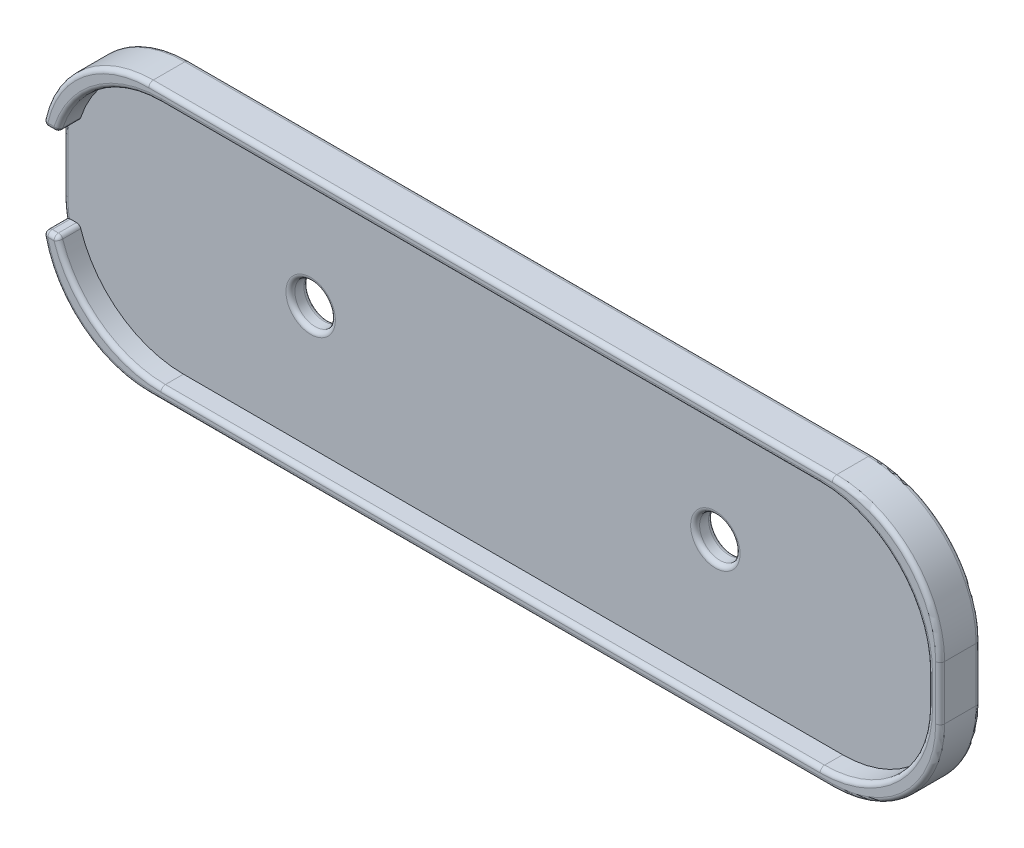
SolidWorks part; units mm, degrees
ref_plane "Front Plane" through (0, 0, 0) normal (0, 0, 1) x (1, 0, 0)
ref_plane "Top Plane" through (0, 0, 0) normal (0, 1, 0) x (1, 0, 0)
ref_plane "Right Plane" through (0, 0, 0) normal (1, 0, 0) x (0, 0, -1)
sketch "Sketch1" plane through (0, 0, 0) normal (0, 0, 1) x (1, 0, 0)
  line L1 (-50, 15) -> (50, 15)
  line L2 (-50, 15) -> (-50, -15)
  line L3 (-50, -15) -> (50, -15)
  line L4 (50, 15) -> (50, -15)
  line L5 (-50, 15) -> (50, -15) construction
  line L6 (-50, -15) -> (50, 15) construction
  point P0 (0, 0)
  dimension "D1" = 30
  dimension "D2" = 100
extrude "Boss-Extrude1" add sketch "Sketch1" along normal blind 2
sketch "Sketch2" plane through (0, 0, 2) normal (0, 0, 1) x (1, 0, 0)
  line L1 (-50, 15) -> (50, 15)
  line L2 (-50, 15) -> (-50, -15)
  line L3 (-50, -15) -> (50, -15)
  line L4 (50, 15) -> (50, -15)
  line L5 (48.65, 13.65) -> (-48.65, 13.65)
  line L6 (48.65, 13.65) -> (48.65, -13.65)
  line L7 (48.65, -13.65) -> (-48.65, -13.65)
  line L8 (-48.65, 13.65) -> (-48.65, -13.65)
  line L9 (48.65, 13.65) -> (-48.65, -13.65) construction
  line L10 (48.65, -13.65) -> (-48.65, 13.65) construction
  point P6 (0, 0)
  dimension "D1" = 1.35
  dimension "D2" = 1.35
extrude "Boss-Extrude2" add sketch "Sketch2" along normal blind 2.5
fillet "Fillet1" radius 12 8 edges at (-50, 15, 2.25) (50, 15, 2.25) (50, -15, 2.25) (-50, -15, 2.25) (48.65, -13.65, 3.25) (-48.65, -13.65, 3.25) (48.65, 13.65, 3.25) (-48.65, 13.65, 3.25)
sketch "Sketch3" plane through (0, 0, 2) normal (0, 0, 1) x (1, 0, 0)
  line L0 (-50, 3) -> (-50, -3) construction
  line L1 (-45, 5) -> (-55, 5)
  line L2 (-45, 5) -> (-45, -5)
  line L3 (-45, -5) -> (-55, -5)
  line L4 (-55, 5) -> (-55, -5)
  line L5 (-45, 5) -> (-55, -5) construction
  line L6 (-45, -5) -> (-55, 5) construction
  point P0 (-50, 0)
  dimension "D1" = 10
  dimension "D2" = 10
extrude "Cut-Extrude1" cut sketch "Sketch3" along normal through all
fillet "Fillet2" radius 0.5 31 edges at (0, -15, 0) (46.4853, -11.4853, 0) (50, 0, 0) (46.4853, 11.4853, 0) (0, 15, 0) (-46.4853, 11.4853, 0) (-50, 0, 0) (-49.958, -4.0035, 2) (-50, 0, 2) (-46.4853, -11.4853, 0) (-49.8322, -5, 3.25) (-48.1729, -5, 3.25) (-49.0025, -5, 4.5) (-48.1729, 5, 3.25) (-49.0025, 5, 4.5) (-49.8322, 5, 3.25) (-49.958, 4.0035, 2) (-43.8542, 11.2469, 4.5) (0, 13.65, 4.5) (-43.8542, -11.2469, 4.5) (0, -13.65, 4.5) (45.1353, -10.1353, 4.5) (48.65, 0, 4.5) (45.1353, 10.1353, 4.5) (-45.746, 12.1652, 4.5) (0, 15, 4.5) (46.4853, 11.4853, 4.5) (50, 0, 4.5) (46.4853, -11.4853, 4.5) (0, -15, 4.5) (-45.746, -12.1652, 4.5)
sketch "Sketch4" plane through (0, 0, 0) normal (0, 0, 1) x (1, 0, 0)
  line L0 (-22.5, 0) -> (22.5, 0) construction
  line L1 (-22.5, 0) -> (-50, 0) construction
  line L2 (-50, -3) -> (-50, 3) construction
  line L3 (22.5, 0) -> (50, 0) construction
  line L4 (50, 3) -> (50, -3) construction
  circle A0 centre (-22.5, 0) radius 2.25
  circle A1 centre (22.5, 0) radius 2.25
  dimension "D1" = 4.5
  dimension "D2" = 45
extrude "Cut-Extrude2" cut sketch "Sketch4" along normal through all
fillet "Fillet3" radius 0.5 4 edges at (24.75, 0, 0) (24.75, 0, 2) (-20.25, 0, 0) (-20.25, 0, 2)
